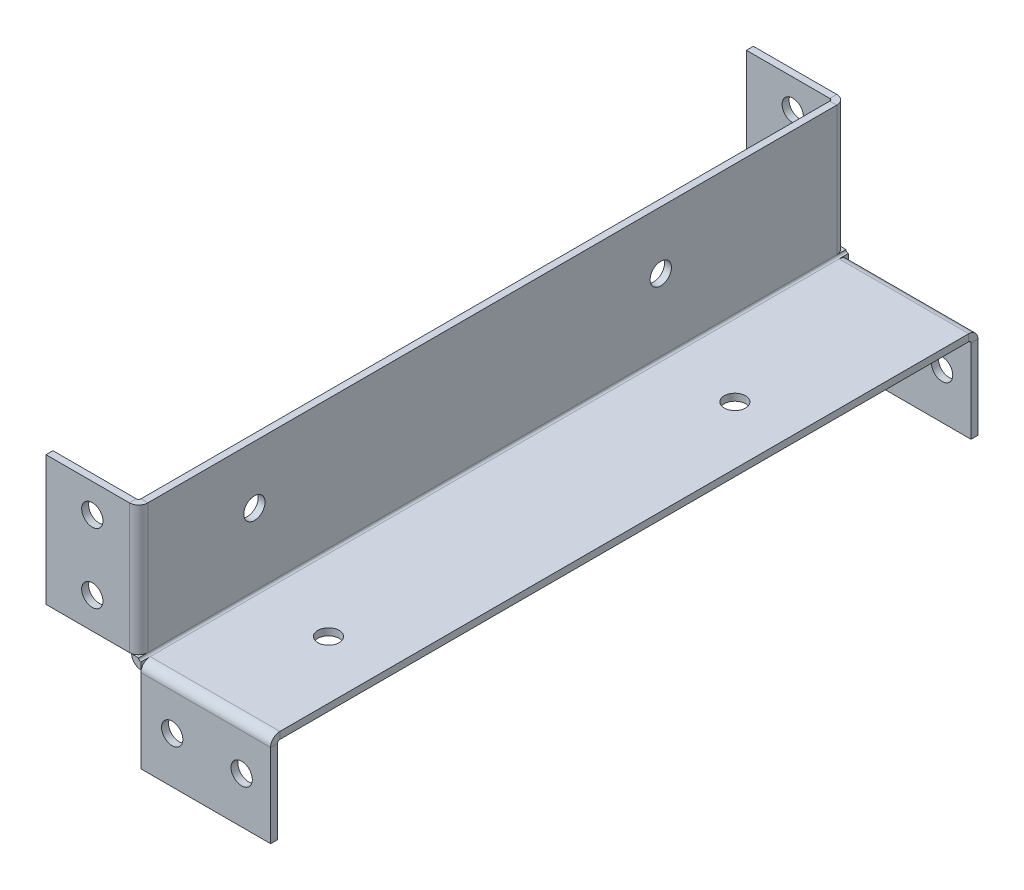
SolidWorks part; units mm, degrees
note: The reader was unsure of these and kept them because the rebuilt part matched: flange length of "Edge-Flange1", "Edge-Flange2".
ref_plane "Front Plane" through (0, 0, 0) normal (0, 0, 1) x (1, 0, 0)
ref_plane "Top Plane" through (0, 0, 0) normal (0, 1, 0) x (1, 0, 0)
ref_plane "Right Plane" through (0, 0, 0) normal (1, 0, 0) x (0, 0, -1)
sketch "Sketch1" plane through (0, 0, 0) normal (0, 1, 0) x (1, 0, 0)
  line L1 (30, 152.75) -> (-30, 152.75)
  line L2 (30, 152.75) -> (30, -152.75)
  line L3 (30, -152.75) -> (-30, -152.75)
  line L4 (-30, 152.75) -> (-30, -152.75)
  line L5 (30, 152.75) -> (-30, -152.75) construction
  line L6 (30, -152.75) -> (-30, 152.75) construction
  point P0 (0, 0)
  dimension "D1" = 60
  dimension "D2" = 305.5
sheet metal parameters "Sheet-Metal1" thickness 3 parameters "D1"=1
base flange "Base-Flange1" sketch "Sketch1" thickness 3 reverse thickness direction yes parameters "D1"=1
edge flange "Edge-Flange1" sketch "Sketch5" flange angle 90 flange length 60 flange position material inside bend radius 1 thickness 3 parameters "D6"=10
sketch "Sketch5" plane through (-30, 3, 0) normal (-1, 0, 0) x (0, 0, 1)
  line L2 (-152.75, 0) -> (-152.75, 57)
  line L3 (-152.75, 57) -> (152.75, 57)
  line L4 (152.75, 57) -> (152.75, 0)
  line L5 (-152.75, 0) -> (152.75, 0) construction
  line L6 (-152.75, 0) -> (152.75, 0)
bend "EdgeBend1" bend radius 1 bend angle 90 parameters "D5"=1
edge flange "Edge-Flange2" sketch "Sketch14" flange profiles "Sketch14", "Sketch15", "Sketch16", "Sketch17" flange angle 90 flange length 40 flange position material inside bend radius 1 thickness 3 relief none parameters "D6"=10, "D8"=0.5
sketch "Sketch14" plane through (-30, 0, 152.75) normal (0, 0, -1) x (0, -1, 0)
  line L1 (-4, 0) -> (-60, 0) construction
  line L2 (-60, 0) -> (-60, 37)
  line L3 (-60, 37) -> (-4, 37)
  line L4 (-4, 37) -> (-4, 0)
  line L5 (-4, 0) -> (-60, 0)
sketch "Sketch15" plane through (0, 0, 152.75) normal (0, 0, -1) x (1, 0, 0)
  line L0 (30, 0) -> (-26, 0) construction
  line L1 (30, 0) -> (-26, 0)
  line L2 (30, 0) -> (30, 37)
  line L3 (30, 37) -> (-26, 37)
  line L4 (-26, 37) -> (-26, 0)
sketch "Sketch16" plane through (-30, 0, -152.75) normal (0, 0, 1) x (0, 1, 0)
  line L0 (60, 0) -> (4, 0) construction
  line L1 (60, 0) -> (4, 0)
  line L2 (60, 0) -> (60, 37)
  line L3 (60, 37) -> (4, 37)
  line L4 (4, 37) -> (4, 0)
sketch "Sketch17" plane through (0, 0, -152.75) normal (0, 0, 1) x (-1, 0, 0)
  line L0 (26, 0) -> (-30, 0) construction
  line L1 (26, 0) -> (-30, 0)
  line L2 (26, 0) -> (26, 37)
  line L3 (26, 37) -> (-30, 37)
  line L4 (-30, 37) -> (-30, 0)
bend "EdgeBend2" bend radius 1 bend angle 90 parameters "D5"=2
bend "EdgeBend3" bend radius 1 bend angle 90 parameters "D5"=3
bend "EdgeBend4" bend radius 1 bend angle 90 parameters "D5"=4
bend "EdgeBend5" bend radius 1 bend angle 90 parameters "D5"=5
sketch "Sketch18" plane through (0, 0, 152.75) normal (0, 0, 1) x (1, 0, 0)
  line L0 (-26, 3) -> (30, 3) construction
  line L1 (-27, 60) -> (-27, 4) construction
  line L2 (-67, 60) -> (-31, 60) construction
  line L3 (30, -1) -> (30, -37) construction
  circle A0 centre (-47, 47.5) radius 4.6
  circle A1 centre (-47, 17.5) radius 4.6
  circle A2 centre (-12.5, -17) radius 4.6
  circle A3 centre (17.5, -17) radius 4.6
  dimension "D7" = 9.2
  dimension "D1" = 30
  dimension "D2" = 30
  dimension "D3" = 20
  dimension "D4" = 20
  dimension "D5" = 12.5
  dimension "D6" = 12.5
extrude "Extrude1" cut sketch "Sketch18" against normal through all normal cut yes
sketch "Sketch19" plane through (-27, 0, 0) normal (1, 0, 0) x (0, 0, -1)
  line L0 (-148.75, 60) -> (148.75, 60) construction
  line L1 (-152.75, 4) -> (-152.75, 60) construction
  line L2 (152.75, 4) -> (152.75, 60) construction
  circle A0 centre (-102.75, 35) radius 4.6
  circle A1 centre (72.75, 35) radius 4.6
  dimension "D4" = 9.2
  dimension "D2" = 80
  dimension "D3" = 50
  dimension "D1" = 25
extrude "Extrude2" cut sketch "Sketch19" against normal blind 3 normal cut yes
sketch "Sketch20" plane through (0, 3, 0) normal (0, 1, 0) x (1, 0, 0)
  line L0 (30, -148.75) -> (30, 148.75) construction
  line L1 (-26, -152.75) -> (30, -152.75) construction
  line L2 (30, 152.75) -> (-26, 152.75) construction
  circle A0 centre (5, 72.75) radius 4.6
  circle A1 centre (5, -102.75) radius 4.6
  dimension "D2" = 9.2
  dimension "D4" = 80
  dimension "D3" = 50
  dimension "D1" = 25
extrude "Extrude3" cut sketch "Sketch20" against normal blind 3 normal cut yes
flat pattern "Flat-Pattern1" [suppressed]
sketch "Bend-Lines1" plane through (0, 4, 0) normal (0, 1, 0) x (-1, 0, 0)
  line L0 (25, -126.4012) -> (-30, -126.4012) construction
  line L1 (82.8023, -126.4012) -> (27.8023, -126.4012) construction
  line L2 (-30, 126.4012) -> (25, 126.4012) construction
  line L3 (27.8023, 126.4012) -> (82.8023, 126.4012) construction
  line L4 (26.4012, -130) -> (26.4012, 130) construction
  line L5 (25, -126.4012) -> (-30, -126.4012) construction
  line L6 (82.8023, -126.4012) -> (27.8023, -126.4012) construction
  line L7 (-30, 126.4012) -> (25, 126.4012) construction
  line L8 (27.8023, 126.4012) -> (82.8023, 126.4012) construction
  line L9 (26.4012, -130) -> (26.4012, 130) construction
bend of the flat pattern "Flatten-<EdgeBend1>1"
bend of the flat pattern "Flatten-<EdgeBend2>1"
bend of the flat pattern "Flatten-<EdgeBend3>1"
bend of the flat pattern "Flatten-<EdgeBend4>1"
bend of the flat pattern "Flatten-<EdgeBend5>1"
